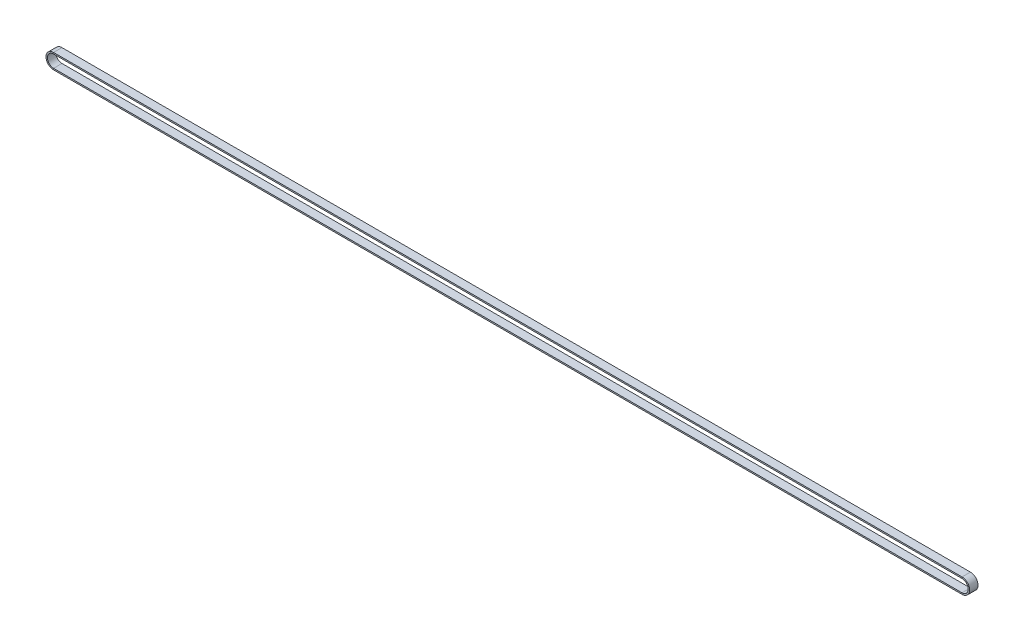
SolidWorks part; units mm, degrees
ref_plane "Front Plane" through (0, 0, 0) normal (0, 0, 1) x (1, 0, 0)
ref_plane "Top Plane" through (0, 0, 0) normal (0, 1, 0) x (1, 0, 0)
ref_plane "Right Plane" through (0, 0, 0) normal (1, 0, 0) x (0, 0, -1)
sketch "Sketch2" plane through (0, 0, 0) normal (0, 0, 1) x (1, 0, 0)
  line L0 (0, 0) -> (1, 0) construction
  line L1 (0, 0) -> (0, 1) construction
  line L2 (-0.0001, 98.3042) -> (-976.331, 98.3042)
  line L3 (-976.331, 114.5837) -> (-0.0001, 114.5837)
  arc A0 (-0.0001, 114.5837) -> (-0.0001, 98.3042) centre (-0.0001, 106.4439) cw
  arc A1 (-976.331, 98.3042) -> (-976.331, 114.5837) centre (-976.331, 106.4439) cw
ref_plane "Plane1" through (-0.0001, 114.5837, 0) normal (1, 0, 0) x (0, 0, -1)
sketch "Sketch3" plane through (-0.0001, 114.5837, 0) normal (1, 0, 0) x (0, 0, -1)
  line L1 (0, -1.5) -> (9, -1.5)
  line L2 (0, -1.5) -> (0, 0)
  line L3 (0, 0) -> (9, 0)
  line L4 (9, -1.5) -> (9, 0)
  dimension "D1" = 1.5
  dimension "D2" = 9
sweep "Sweep1" add profiles "Sketch3" path "Sketch2"
